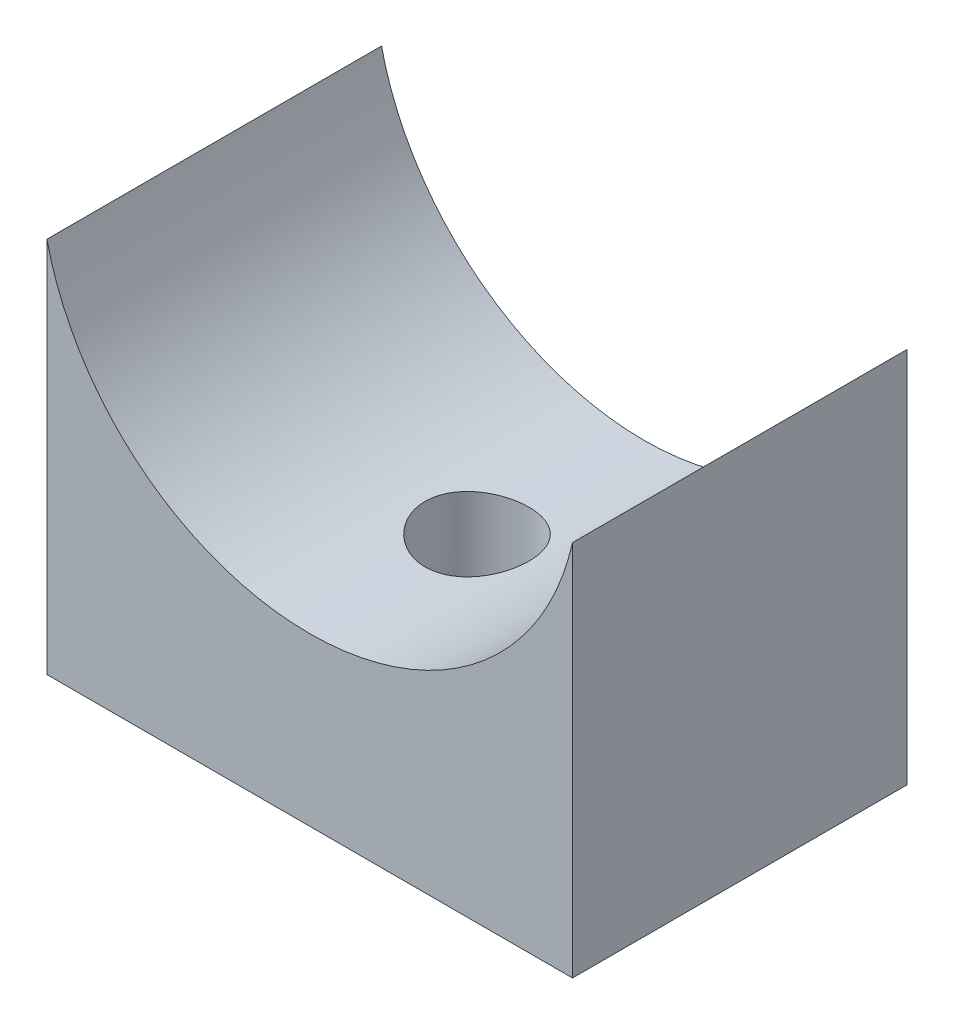
SolidWorks part; units mm, degrees
ref_plane "Front Plane" through (0, 0, 0) normal (0, 0, 1) x (1, 0, 0)
ref_plane "Top Plane" through (0, 0, 0) normal (0, 1, 0) x (1, 0, 0)
ref_plane "Right Plane" through (0, 0, 0) normal (1, 0, 0) x (0, 0, -1)
sketch "Sketch1" plane through (0, 0, 0) normal (0, 0, 1) x (1, 0, 0)
  line L0 (-7.8539, -11.27) -> (7.8539, -11.27)
  line L1 (7.8539, 0) -> (7.8539, -11.27)
  line L2 (-7.8539, 0) -> (-7.8539, -11.27)
  line L3 (55, 0) -> (-55, 0) construction
  line L4 (0, -44.7868) -> (0, 44.7868) construction
  arc A0 (-7.8539, 0) -> (7.8539, 0) centre (0, 1.7659) ccw
  dimension "D1" = 8.05
  dimension "D2" = 11.27
extrude "Boss-Extrude1" add sketch "Sketch1" along normal mid plane 10
sketch "Sketch2" plane through (0, -11.27, 0) normal (0, -1, 0) x (-1, 0, 0)
  circle A0 centre (0, 0) radius 1.55
  dimension "D1" = 3.1
extrude "Cut-Extrude1" cut sketch "Sketch2" against normal up to surface (4.9859 mm away) up to face at (0, -3.142, 0)
equation "\"tubeDiam\" = 8.05"
equation "\"D1@Sketch1\"=\"tubeDiam\""
equation "\"D2@Sketch1\"=\"tubeDiam\"+(\"tubeDiam\"*2/5)"
